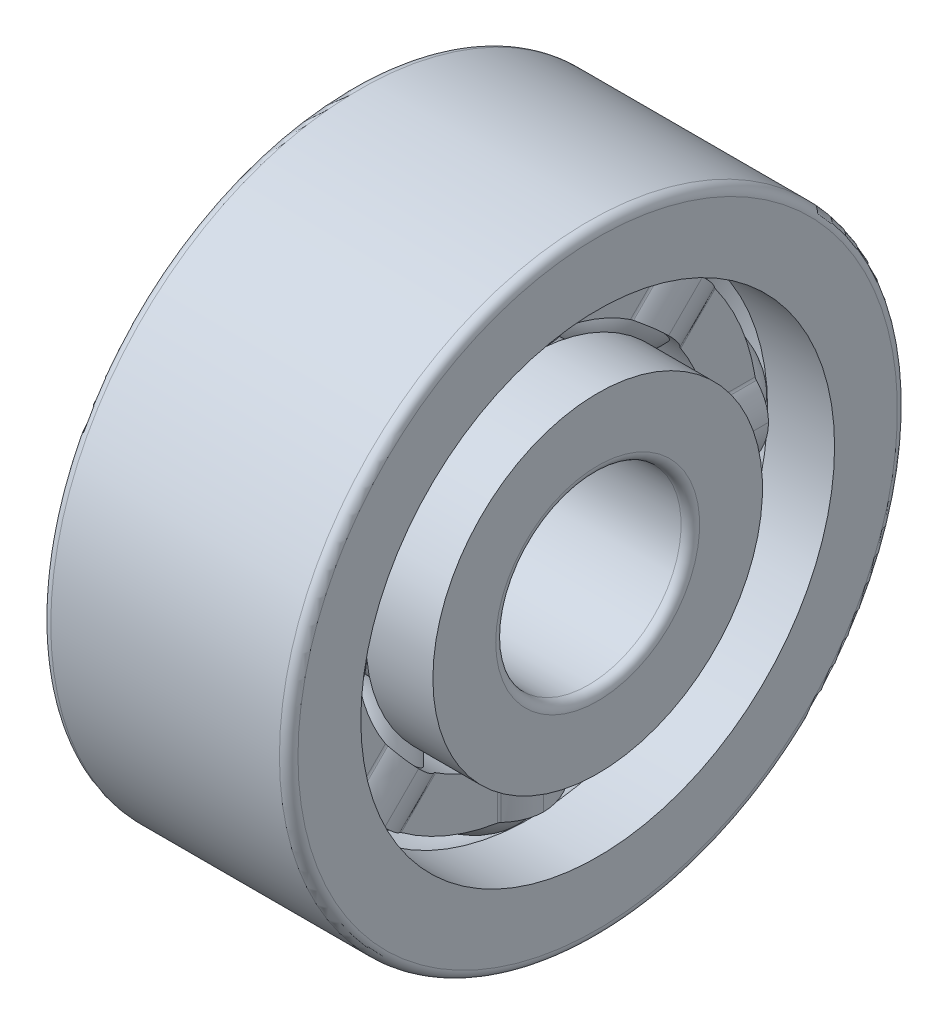
SolidWorks part; units mm, degrees
ref_plane "Front" through (0, 0, 0) normal (0, 0, 1) x (1, 0, 0)
ref_plane "Top" through (0, 0, 0) normal (0, 1, 0) x (1, 0, 0)
ref_plane "Right" through (0, 0, 0) normal (1, 0, 0) x (0, 0, -1)
sketch "Support-Front-Body" plane through (0, 0, 0) normal (0, 0, 1) x (1, 0, 0)
  line L0 (-2, 0) -> (2, 0) construction
  line L1 (2, 0) -> (2, 1.5) construction
  line L2 (-2, 0) -> (-2, 1.5) construction
  line L4 (-2, 5) -> (2, 5)
  line L5 (-2, 5) -> (-2, 3.8333)
  line L6 (-2, 3.8333) -> (2, 3.8333)
  line L7 (2, 5) -> (2, 3.8333)
  line L8 (-2, 2.6667) -> (2, 2.6667)
  line L9 (-2, 2.6667) -> (-2, 1.5)
  line L10 (-2, 1.5) -> (2, 1.5)
  line L11 (2, 2.6667) -> (2, 1.5)
  line L13 (-2, 3.25) -> (2, 3.25) construction
  line L14 (0, 0) -> (0, 1.5) construction
  line L15 (0, 1.5) -> (0, 2.6667) construction
  line L16 (0, 2.6667) -> (0, 3.8333) construction
  line L17 (0, 3.8333) -> (0, 5) construction
  dimension "Diam-Inner" = 3
  dimension "Diam-Outer" = 10
  dimension "CC-Ball" = 6.5
  dimension "Width-Inner" = 4
sketch "Support-Front-Ball" plane through (0, 0, 0) normal (0, 0, 1) x (1, 0, 0)
  line L0 (-1.05, 3.25) -> (1.05, 3.25) construction
  line L1 (0, 0) -> (0, 2.2) construction
  line L2 (-2, 3.25) -> (2, 3.25) construction
  line L3 (0, 3.25) -> (0, 4.3) construction
  line L6 (0, 2.2) -> (0, 3.25) construction
  circle A0 centre (0, 3.25) radius 1.05
  dimension "Diam-Ball" = 2.1
sketch "Support-Front-Groove" plane through (0, 0, 0) normal (0, 0, 1) x (1, 0, 0)
  line L0 (0, 3.8333) -> (0, 3.6389) construction
  line L1 (0, 3.6389) -> (0, 3.4444) construction
  line L2 (0, 3.4444) -> (0, 3.25) construction
  line L3 (-2, 3.25) -> (2, 3.25) construction
  line L4 (-1.05, 3.25) -> (1.05, 3.25) construction
  line L6 (-2, 3.8333) -> (2, 3.8333) construction
  line L7 (0, 2.2429) -> (0, 2.2) construction
  line L8 (0.8731, 2.6667) -> (0.9159, 2.6667) construction
  line L9 (-2, 2.6667) -> (2, 2.6667) construction
  line L11 (0, 0) -> (0, 2.2) construction
  line L12 (-1.05, 3.25) -> (1.05, 3.25) construction
  circle A0 centre (0, 3.25) radius 1.05 construction
  circle A1 centre (0, 3.4444) radius 1.2016
  circle A2 centre (0, 3.0556) radius 1.2016
sketch "Support-Front-Ball-Cage" plane through (0, 0, 0) normal (0, 0, 1) x (1, 0, 0)
  line L0 (1.05, 3.25) -> (-1.1251, 3.25) construction
  line L1 (-1.1251, 3.6389) -> (1.1251, 3.6389)
  line L2 (-1.1251, 3.6389) -> (-1.1251, 2.8611)
  line L3 (-1.1251, 2.8611) -> (1.1251, 2.8611)
  line L4 (1.1251, 3.6389) -> (1.1251, 2.8611)
  line L5 (-2, 3.25) -> (2, 3.25) construction
  line L6 (0, 2.8611) -> (0, 3.6389) construction
  line L7 (0, 2.6667) -> (0, 3.8333) construction
  line L8 (1.05, 3.25) -> (1.1251, 3.25) construction
  line L9 (1.0876, 3.25) -> (1.0876, 3.4444) construction
  line L10 (1.0876, 3.4444) -> (1.0876, 3.6389) construction
  line L11 (1.0876, 3.6389) -> (1.0876, 3.8333) construction
  line L12 (-2, 3.8333) -> (2, 3.8333) construction
  line L13 (1.1251, 3.7361) -> (0.9307, 3.7361) construction
  line L14 (0, 3.6389) -> (0, 4.3751) construction
  circle A0 centre (0, 3.25) radius 1.05 construction
  circle A1 centre (0, 3.25) radius 1.1251 construction
  point P26 (1.0876, 3.7361)
sketch "Support-Right-Ball-Cage" plane through (0, 0, 0) normal (1, 0, 0) x (0, 0, -1)
  line L0 (0, 0) -> (0, 5) construction
  line L1 (0, 0) -> (-3.5355, 3.5355) construction
  line L2 (0, 2.1249) -> (-1.5025, 1.5025) construction
  line L3 (-3.0937, 3.0937) -> (0, 4.3751) construction
  line L4 (0, 0) -> (-2.0929, 4.5409) construction
  line L6 (-1.731, 4.6908) -> (0, 0) construction
  circle A0 centre (0, 0) radius 2.8611
  circle A1 centre (0, 0) radius 3.6389
  circle A2 centre (0, 3.25) radius 1.1251
  circle A3 centre (0, 0) radius 3.25 construction
  circle A4 centre (-2.2981, 2.2981) radius 1.1251
  dimension "Angle-Ball" = 45
ref_plane "Ref-Plane-1" through (0, 1.8137, 0.7513) normal (0, 0.9239, 0.3827) x (-1, 0, 0)
sketch "Support-Ball-Gage-Inner" plane through (0, 1.8137, 0.7513) normal (0, 0.9239, 0.3827) x (-1, 0, 0)
  line L0 (-0.9546, -0.1908) -> (-0.9546, 0.1908)
  line L1 (0.9546, -0.1908) -> (0.9546, 0.1908)
  line L2 (1.1251, 0.8131) -> (1.1251, -0.8131)
  line L3 (-1.1251, 0) -> (-0.9546, 0) construction
  line L4 (-1.05, -1.2437) -> (-1.05, -0.1908) construction
  line L5 (-1.05, -0.1908) -> (-0.9546, -0.1908) construction
  line L6 (-1.05, -0.1908) -> (-1.05, -0.0954) construction
  line L7 (-1.05, -0.0954) -> (-1.05, 0) construction
  line L8 (-0.9546, 0) -> (0, 0) construction
  line L9 (-1.1251, 0.8131) -> (-1.1251, -0.8131)
  line L10 (-1.1251, -1.3925) -> (-1.1251, -1.0949) construction
  line L11 (-1.05, -0.0954) -> (-0.9546, -0.1908) construction
  line L12 (0, 0.8131) -> (0, -0.8131) construction
  arc A0 (-1.1251, -0.8131) -> (-0.9679, -0.2395) centre (0, -0.8131) cw
  arc A1 (-0.9679, -0.2395) -> (-0.9546, -0.1908) centre (-1.05, -0.1908) ccw
  arc A2 (-0.9546, 0.1908) -> (-0.9679, 0.2395) centre (-1.05, 0.1908) ccw
  arc A3 (-0.9679, 0.2395) -> (-1.1251, 0.8131) centre (0, 0.8131) cw
  arc A4 (0.9679, 0.2395) -> (1.1251, 0.8131) centre (0, 0.8131) ccw
  arc A5 (0.9546, 0.1908) -> (0.9679, 0.2395) centre (1.05, 0.1908) cw
  arc A6 (0.9679, -0.2395) -> (0.9546, -0.1908) centre (1.05, -0.1908) cw
  arc A7 (1.1251, -0.8131) -> (0.9679, -0.2395) centre (0, -0.8131) ccw
  dimension "D1" = 45
ref_plane "Ref-Plane-2" through (0, 3.7344, 1.5468) normal (0, -0.9239, -0.3827) x (1, 0, 0)
sketch "Support-Ball-Gage-Outer" plane through (0, 3.7344, 1.5468) normal (0, -0.9239, -0.3827) x (1, 0, 0)
  line L0 (1.1251, 1.6743) -> (1.1251, -1.6743)
  line L1 (0.9546, -1.052) -> (0.9546, 1.052)
  line L2 (1.1251, 0.8131) -> (1.1251, -0.8131) construction
  line L7 (0.9546, -0.1908) -> (0.9546, 0.1908) construction
  line L8 (0, 1.6743) -> (0, -1.6743) construction
  line L9 (-1.1251, 1.6743) -> (-1.1251, -1.6743)
  line L10 (-0.9546, -1.052) -> (-0.9546, 1.052)
  arc A0 (1.1251, -1.6743) -> (0.9679, -1.1006) centre (0, -1.6743) ccw
  arc A1 (0.9679, -1.1006) -> (0.9546, -1.052) centre (1.05, -1.052) cw
  arc A2 (0.9546, 1.052) -> (0.9679, 1.1006) centre (1.05, 1.052) cw
  arc A3 (0.9679, 1.1006) -> (1.1251, 1.6743) centre (0, 1.6743) ccw
  arc A4 (0.9679, 0.2395) -> (0.9546, 0.1908) centre (1.05, 0.1908) ccw construction
  arc A5 (-0.9679, -1.1006) -> (-0.9546, -1.052) centre (-1.05, -1.052) ccw
  arc A6 (-1.1251, -1.6743) -> (-0.9679, -1.1006) centre (0, -1.6743) cw
  arc A7 (-0.9679, 1.1006) -> (-1.1251, 1.6743) centre (0, 1.6743) cw
  arc A8 (-0.9546, 1.052) -> (-0.9679, 1.1006) centre (-1.05, 1.052) ccw
ref_axis "Ref-Axis" through (-2.75, 0, 0) along (1, 0, 0)
ref_plane "Ref-Plane-Right" through (2, 0, 0) normal (1, 0, 0) x (0, 0, -1)
ref_plane "Ref-Plane-Left" through (-2, 0, 0) normal (1, 0, 0) x (0, 0, -1)
sketch "Sketch7" plane through (0, 0, 0) normal (0, 0, 1) x (1, 0, 0)
  line L0 (-1.05, 3.25) -> (1.05, 3.25) construction
  line L2 (-1.05, 3.25) -> (1.05, 3.25) construction
  line L4 (-1.05, 3.25) -> (1.05, 3.25)
  circle A0 centre (0, 3.25) radius 1.05 construction
  arc A1 (-1.05, 3.25) -> (1.05, 3.25) centre (0, 3.25) ccw
revolve "Body-Ball" add sketch "Sketch7" angle 360 about L2
sketch "Sketch10" plane through (0, 0, 0) normal (0, 0, 1) x (1, 0, 0)
  line L0 (-2, 0) -> (2, 0) construction
  line L1 (-1.1251, 3.6389) -> (-1.1251, 2.8611) construction
  line L2 (-1.1251, 3.6389) -> (1.1251, 3.6389) construction
  line L3 (1.1251, 3.6389) -> (1.1251, 2.8611) construction
  line L4 (-1.1251, 2.8611) -> (1.1251, 2.8611) construction
  line L5 (-2, 0) -> (2, 0) construction
  line L6 (-1.1251, 3.6389) -> (-1.1251, 2.8611)
  line L7 (-1.1251, 3.6389) -> (1.1251, 3.6389)
  line L8 (1.1251, 3.6389) -> (1.1251, 2.8611)
  line L9 (-1.1251, 2.8611) -> (1.1251, 2.8611)
revolve "Body-Ball-Cage" add sketch "Sketch10" angle 360 about L5
sketch "Sketch16" plane through (0, 1.8137, 0.7513) normal (0, 0.9239, 0.3827) x (-1, 0, 0)
  line L0 (0.9546, -0.1908) -> (0.9546, 0.1908) construction
  line L1 (1.1251, 0.8131) -> (1.1251, -0.8131) construction
  line L2 (0.9546, -0.1908) -> (0.9546, 0.1908)
  line L3 (1.1251, 0.8131) -> (1.1251, -0.8131)
  arc A0 (0.9679, 0.2395) -> (1.1251, 0.8131) centre (0, 0.8131) ccw construction
  arc A1 (0.9679, 0.2395) -> (0.9546, 0.1908) centre (1.05, 0.1908) ccw construction
  arc A2 (0.9546, -0.1908) -> (0.9679, -0.2395) centre (1.05, -0.1908) ccw construction
  arc A3 (1.1251, -0.8131) -> (0.9679, -0.2395) centre (0, -0.8131) ccw construction
  arc A4 (0.9679, 0.2395) -> (1.1251, 0.8131) centre (0, 0.8131) ccw
  arc A5 (0.9679, 0.2395) -> (0.9546, 0.1908) centre (1.05, 0.1908) ccw
  arc A6 (0.9546, -0.1908) -> (0.9679, -0.2395) centre (1.05, -0.1908) ccw
  arc A7 (1.1251, -0.8131) -> (0.9679, -0.2395) centre (0, -0.8131) ccw
sketch "Sketch17" plane through (0, 3.7344, 1.5468) normal (0, -0.9239, -0.3827) x (1, 0, 0)
  line L0 (-0.9546, -1.052) -> (-0.9546, 1.052) construction
  line L1 (-1.1251, 1.6743) -> (-1.1251, -1.6743) construction
  line L2 (-0.9546, -1.052) -> (-0.9546, 1.052)
  line L3 (-1.1251, 1.6743) -> (-1.1251, -1.6743)
  arc A0 (-1.1251, 1.6743) -> (-0.9679, 1.1006) centre (0, 1.6743) ccw construction
  arc A1 (-0.9546, 1.052) -> (-0.9679, 1.1006) centre (-1.05, 1.052) ccw construction
  arc A2 (-0.9679, -1.1006) -> (-0.9546, -1.052) centre (-1.05, -1.052) ccw construction
  arc A3 (-0.9679, -1.1006) -> (-1.1251, -1.6743) centre (0, -1.6743) ccw construction
  arc A4 (-1.1251, 1.6743) -> (-0.9679, 1.1006) centre (0, 1.6743) ccw
  arc A5 (-0.9546, 1.052) -> (-0.9679, 1.1006) centre (-1.05, 1.052) ccw
  arc A6 (-0.9679, -1.1006) -> (-0.9546, -1.052) centre (-1.05, -1.052) ccw
  arc A7 (-0.9679, -1.1006) -> (-1.1251, -1.6743) centre (0, -1.6743) ccw
loft "Cut-Ball-Cage-1" cut profiles "Sketch16", "Sketch17"
sketch "Sketch14" plane through (0, 1.8137, 0.7513) normal (0, 0.9239, 0.3827) x (-1, 0, 0)
  line L0 (-0.9546, -0.1908) -> (-0.9546, 0.1908) construction
  line L1 (-1.1251, 0.8131) -> (-1.1251, -0.8131) construction
  line L2 (-0.9546, -0.1908) -> (-0.9546, 0.1908)
  line L3 (-1.1251, 0.8131) -> (-1.1251, -0.8131)
  arc A0 (-1.1251, 0.8131) -> (-0.9679, 0.2395) centre (0, 0.8131) ccw construction
  arc A1 (-0.9546, 0.1908) -> (-0.9679, 0.2395) centre (-1.05, 0.1908) ccw construction
  arc A2 (-0.9679, -0.2395) -> (-0.9546, -0.1908) centre (-1.05, -0.1908) ccw construction
  arc A3 (-0.9679, -0.2395) -> (-1.1251, -0.8131) centre (0, -0.8131) ccw construction
  arc A4 (-1.1251, 0.8131) -> (-0.9679, 0.2395) centre (0, 0.8131) ccw
  arc A5 (-0.9546, 0.1908) -> (-0.9679, 0.2395) centre (-1.05, 0.1908) ccw
  arc A6 (-0.9679, -0.2395) -> (-0.9546, -0.1908) centre (-1.05, -0.1908) ccw
  arc A7 (-0.9679, -0.2395) -> (-1.1251, -0.8131) centre (0, -0.8131) ccw
sketch "Sketch15" plane through (0, 3.7344, 1.5468) normal (0, -0.9239, -0.3827) x (1, 0, 0)
  line L0 (0.9546, -1.052) -> (0.9546, 1.052) construction
  line L1 (1.1251, 1.6743) -> (1.1251, -1.6743) construction
  line L2 (0.9546, -1.052) -> (0.9546, 1.052)
  line L3 (1.1251, 1.6743) -> (1.1251, -1.6743)
  arc A0 (0.9679, 1.1006) -> (1.1251, 1.6743) centre (0, 1.6743) ccw construction
  arc A1 (0.9679, 1.1006) -> (0.9546, 1.052) centre (1.05, 1.052) ccw construction
  arc A2 (0.9546, -1.052) -> (0.9679, -1.1006) centre (1.05, -1.052) ccw construction
  arc A3 (1.1251, -1.6743) -> (0.9679, -1.1006) centre (0, -1.6743) ccw construction
  arc A4 (0.9679, 1.1006) -> (1.1251, 1.6743) centre (0, 1.6743) ccw
  arc A5 (0.9679, 1.1006) -> (0.9546, 1.052) centre (1.05, 1.052) ccw
  arc A6 (0.9546, -1.052) -> (0.9679, -1.1006) centre (1.05, -1.052) ccw
  arc A7 (1.1251, -1.6743) -> (0.9679, -1.1006) centre (0, -1.6743) ccw
loft "Cut-Ball-Cage-2" cut profiles "Sketch15", "Sketch14"
pattern_circular "Pattern-Ball" count 8 over 360 about axis through (-2.75, 0, 0) along (1, 0, 0) of "Body-Ball", "Cut-Ball-Cage-2", "Cut-Ball-Cage-1"
sketch "Sketch2" plane through (0, 0, 0) normal (0, 0, 1) x (1, 0, 0)
  line L4 (-2, 2.6667) -> (-2, 1.5) construction
  line L5 (-2, 2.6667) -> (2, 2.6667) construction
  line L6 (2, 2.6667) -> (2, 1.5) construction
  line L7 (-2, 1.5) -> (2, 1.5) construction
  line L8 (-2, 0) -> (2, 0) construction
  line L9 (-2, 0) -> (2, 0) construction
  line L10 (-2, 2.6667) -> (-2, 1.5)
  line L11 (-2, 2.6667) -> (-0.9159, 2.6667)
  line L12 (2, 2.6667) -> (2, 1.5)
  line L13 (-2, 1.5) -> (2, 1.5)
  line L14 (0.9159, 2.6667) -> (2, 2.6667)
  circle A1 centre (0, 3.4444) radius 1.2016 construction
  arc A2 (-0.9159, 2.6667) -> (0.9159, 2.6667) centre (0, 3.4444) ccw
sketch "Sketch8" plane through (0, 0, 0) normal (0, 0, 1) x (1, 0, 0)
  line L0 (-2, 0) -> (2, 0) construction
  line L1 (-2, 5) -> (-2, 3.8333) construction
  line L2 (-2, 3.8333) -> (2, 3.8333) construction
  line L3 (2, 5) -> (2, 3.8333) construction
  line L4 (-2, 0) -> (2, 0) construction
  line L9 (-2, 5) -> (2, 5) construction
  line L10 (-2, 5) -> (-2, 3.8333)
  line L11 (-2, 3.8333) -> (-0.9159, 3.8333)
  line L12 (2, 5) -> (2, 3.8333)
  line L13 (-2, 5) -> (2, 5)
  line L14 (0.9159, 3.8333) -> (2, 3.8333)
  circle A1 centre (0, 3.0556) radius 1.2016 construction
  arc A2 (0.9159, 3.8333) -> (-0.9159, 3.8333) centre (0, 3.0556) ccw
revolve "Body-Inner" add sketch "Sketch2" angle 360 about L9
revolve "Body-Outer" add sketch "Sketch8" angle 360 about L4
fillet "Cosmetic-Fillet-Outer-1" radius 0.15 1 edges at (-2, 0, 5)
fillet "Cosmetic-Fillet-Outer-2" radius 0.15 1 edges at (2, 0, 5)
fillet "Cosmetic-Fillet-Inner-1" radius 0.15 1 edges at (-2, 0, 1.5)
fillet "Cosmetic-Fillet-Inner-2" radius 0.15 1 edges at (2, 0, 1.5)
equation "\"Diam-Ball@Support-Front-Ball\"=(((\"Diam-Outer@Support-Front-Body\"-\"Diam-Inner@Support-Front-Body\")/2)*3)/5"
equation "\"Num-Ball@Pattern-Ball\"=INT((PI*(\"Diam-Outer@Support-Front-Body\"-((\"Diam-Outer@Support-Front-Body\"-\"Diam-Inner@Support-Front-Body\")/2)))/(\"Diam-Ball@Support-Front-Ball\"*1.2))"
equation "\"Angle-Ball@Support-Right-Ball-Cage\" = 360 / INT(((PI*(\"Diam-Outer@Support-Front-Body\"-((\"Diam-Outer@Support-Front-Body\"-\"Diam-Inner@Support-Front-Body\")/4)))/2)/\"Diam-Ball@Support-Front-Ball\")"
equation "\"Angle-Ball@Support-Right-Ball-Cage\" = 360 / \"Num-Ball@Pattern-Ball\""
